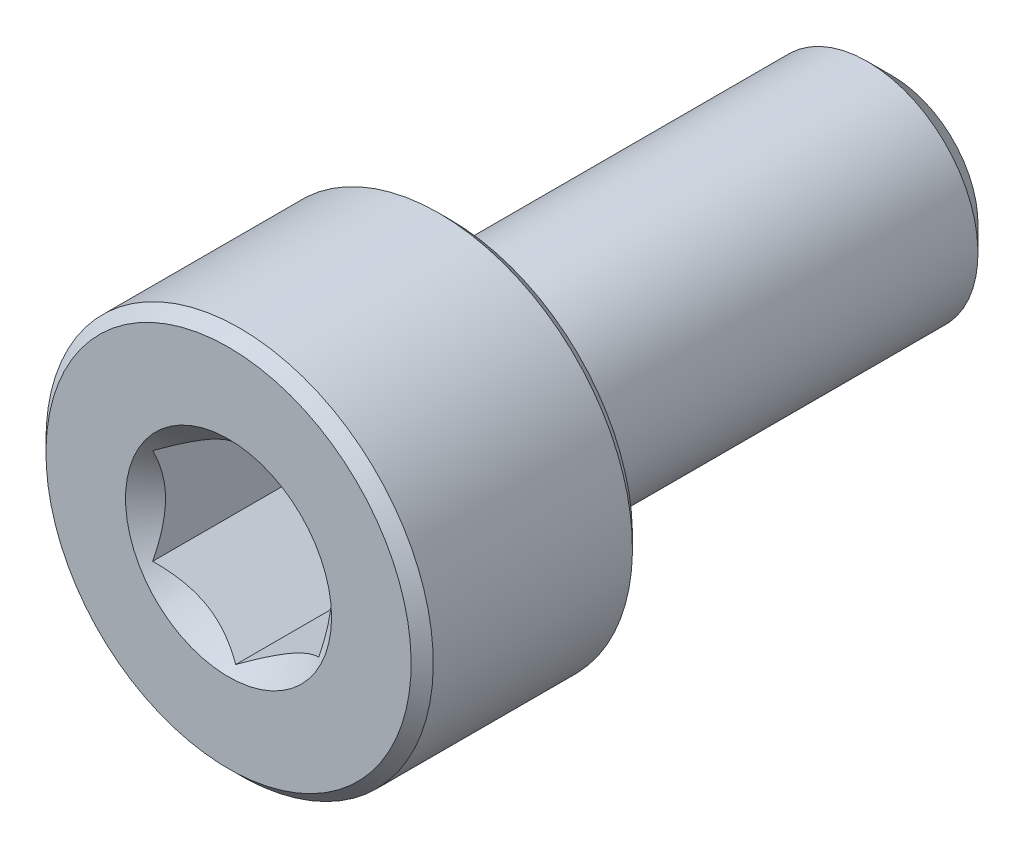
SolidWorks part; units mm, degrees
ref_plane "Front Plane" through (0, 0, 0) normal (0, 0, 1) x (1, 0, 0)
ref_plane "Top Plane" through (0, 0, 0) normal (0, 1, 0) x (1, 0, 0)
ref_plane "Right Plane" through (0, 0, 0) normal (1, 0, 0) x (0, 0, -1)
sketch "Sketch1" plane through (0, 0, 0) normal (1, 0, 0) x (0, 0, -1)
  line L0 (-6, 0) -> (6, 0) construction
  line L1 (6, 0) -> (6, 1.5453) construction
  line L2 (6, 1.5453) -> (5.5453, 2) construction
  line L3 (5.5453, 2) -> (5.475, 2) construction
  line L4 (5.475, 2) -> (-2, 2) construction
  line L5 (-2, 2) -> (-2, 3.5) construction
  line L6 (-2, 3.5) -> (-6, 3.5) construction
  line L7 (-6, 3.5) -> (-6, 0) construction
  line L8 (6, 1.5453) -> (6, 2) construction
  line L9 (5.9562, 2.0758) -> (6.3062, 1.4696) construction
  line L10 (6.3062, 1.4696) -> (6.6562, 2.0758) construction
  line L11 (6.6562, 2.0758) -> (5.9562, 2.0758) construction
  line L12 (6.3062, 2.0758) -> (6.3063, 2) construction
  line L13 (6.3062, 1.4696) -> (6.3062, 1.5453) construction
  line L14 (6.2625, 1.5453) -> (6.35, 1.5453) construction
  line L15 (6, 2) -> (6.6125, 2) construction
  line L16 (5.9781, 2.0379) -> (6.6344, 2.0379) construction
  line L17 (6, 0) -> (6, -2) construction
  line L18 (-2.2, 3.5) -> (-2, 3.3) construction
  line L19 (-5.8, 3.5) -> (-6, 3.3) construction
  line L20 (-2, 2) -> (-2, 0) construction
  line L21 (-2, 1) -> (0.6667, 1) construction
  line L22 (0.6667, 1) -> (3.3333, 1) construction
  line L23 (3.3333, 1) -> (6, 1) construction
  line L24 (0.6667, 1) -> (0.6667, 2) construction
  line L25 (0.6667, 2) -> (0.6667, 3.5) construction
  line L26 (3.3333, 1) -> (3.3333, 3.5) construction
  point P0 (-6, 1.5)
  point P3 (4.25, 2)
  point P4 (0, 0)
  point P18 (3.3333, 2)
  point P22 (6.3062, 1.5453)
  point P24 (5.475, 2)
  point P25 (6.3063, 2)
  point P28 (6.3063, 2.0379)
  point P29 (4.25, -2)
  point P30 (0.6667, 2)
  point P31 (-4, 3.5)
  point P37 (-2.7, 3.5)
  point P38 (-5.7, 3.5)
  point P45 (0.6667, 1)
  point P46 (3.3333, 1)
  dimension "D2" = 0.0875
  dimension "D7" = 0.2
  dimension "D8" = 0.2
  dimension "D9" = 0.2
  dimension "D10" = 0.1
  dimension "D11" = 0.5
  dimension "Drive Size" = 3
  dimension "Head Diameter" = 7
  dimension "Head Height" = 4
  dimension "Thread Pitch" = 0.7
  dimension "Thread Size" = 4
  dimension "Length" = 8
  dimension "D12" = 0.525
  dimension "D4" = 1.75
  dimension "D3" = 45
sketch "Sketch2" plane through (0, 0, 0) normal (1, 0, 0) x (0, 0, -1)
  line L0 (-6, 0) -> (-6, 3.3)
  line L1 (-5.8, 3.5) -> (-2.2, 3.5)
  line L2 (-2, 3.3) -> (-2, 2.2)
  line L4 (5.5453, 2) -> (6, 1.5453)
  line L5 (6, 1.5453) -> (6, 0)
  line L6 (-2, 3.5) -> (-6, 3.5) construction
  line L7 (6, 0) -> (-6, 0)
  line L8 (-5.8, 3.5) -> (-6, 3.3) construction
  line L10 (-5.8, 3.5) -> (-6, 3.3)
  line L14 (-2.2, 3.5) -> (-2, 3.3) construction
  line L16 (-2.2, 3.5) -> (-2, 3.3)
  line L17 (-2, 2) -> (-2, 3.5) construction
  line L19 (-1.8, 2) -> (5.5453, 2)
  line L20 (5.475, 2) -> (-2, 2) construction
  arc A1 (-2, 2.2) -> (-1.8, 2) centre (-1.8, 2.2) ccw
  dimension "D3" = 0.2
revolve "Revolve1" add sketch "Sketch2" angle 360 about L7
sketch "Sketch3" plane through (0, 0, 6) normal (0, 0, 1) x (1, 0, 0)
  line L1 (1.5, -0.866) -> (1.5, 0.866)
  line L2 (1.5, 0.866) -> (0, 1.7321)
  line L3 (0, 1.7321) -> (-1.5, 0.866)
  line L4 (-1.5, 0.866) -> (-1.5, -0.866)
  line L5 (-1.5, -0.866) -> (0, -1.7321)
  line L6 (0, -1.7321) -> (1.5, -0.866)
  circle A0 centre (0, 0) radius 1.5 construction
  circle A1 centre (0, 0) radius 3.5 construction
  circle A2 centre (0, 0) radius 3.5 construction
  circle A3 centre (0, 0) radius 1.7321 construction
  point P13 (0, 0)
  dimension "D1" = 3.4641
extrude "Cut-Extrude1" cut sketch "Sketch3" against normal offset from surface (3 mm away) 1 up to face at (0, 3.3, 2)
sketch "Sketch4" plane through (0, 0, 6) normal (0, 0, 1) x (1, 0, 0)
  circle A0 centre (0, 0) radius 1.862
  dimension "D1" = 3.7239
extrude "Cut-Extrude2" cut sketch "Sketch4" against normal up to vertex (2 mm away) draft 45 up to point (0, 3.5, 4)
sketch "Sketch11" plane through (0, 0, 0) normal (1, 0, 0) x (0, 0, -1)
  line L0 (-6, 0) -> (6, 0) construction
  line L1 (-6, 0) -> (6, 0) construction
  line L2 (-0.5, 0) -> (-0.5, 2) construction
  line L3 (5.475, 2) -> (-2, 2) construction
  line L4 (4.5, 0) -> (4.5, 2) construction
  line L6 (6, 1.5453) -> (6, 2) construction
  point P2 (-0.5, 0)
  point P3 (4.5, 0)
  dimension "D1" = 1.5
  dimension "D2" = 1.5
sketch "Sketch6" [suppressed] plane through (0, 0, -6) normal (0, 0, -1) x (-1, 0, 0)
  circle A0 centre (0, 0) radius 2
curve "Helix/Spiral1" [suppressed] pitch 0.7 height 8.7 turns 12.4286
sketch "Sketch10" [suppressed] plane through (0, 0, 0) normal (1, 0, 0) x (0, 0, -1)
  line L0 (-1.8, -3.5) -> (-1.8, 3.5)
  line L5 (-6, 0) -> (6, 0) construction
  line L6 (-1.8, 2) -> (-1.8, -2) construction
  point P3 (-1.8, 0)
split "Split1" [suppressed] bodies to split 106
sketch "Sketch7" [suppressed] plane through (0, 0, 0) normal (1, 0, 0) x (0, 0, -1)
  line L0 (5.9781, 2.0379) -> (6.6344, 2.0379)
  line L1 (6.6344, 2.0379) -> (6.35, 1.5453)
  line L2 (6.35, 1.5453) -> (6.2625, 1.5453)
  line L3 (6.2625, 1.5453) -> (5.9781, 2.0379)
sweep "Cut-Sweep1" [suppressed] cut profiles "Sketch7" path "Helix/Spiral1"
sketch "Sketch8" [suppressed] plane through (0, 0, 0) normal (1, 0, 0) x (0, 0, -1)
  line L0 (-2, 0) -> (-2, 2)
  line L1 (-1.8, -2) -> (-1.8, 2) construction
  line L2 (-2, 2) -> (-1.8, 2)
  line L4 (-1.8, 2) -> (-0.6453, 0)
  line L5 (-0.6453, 0) -> (-2, 0)
  line L6 (5.475, 2) -> (-2, 2) construction
  line L7 (-6, 0) -> (6, 0) construction
  dimension "D1" = 60
revolve "Revolve2" [suppressed] add sketch "Sketch8" angle 360 about L5
equation "\"D2@Sketch1\" = \"Thread Pitch@Sketch1\" / 8"
equation "\"D4@Helix/Spiral1\" = \"Thread Pitch@Sketch1\""
equation "\"D7@Sketch1\" = \"Head Height@Sketch1\" * .05"
equation "\"D8@Sketch1\"=\"D7@Sketch1\""
equation "\"D9@Sketch1\"=\"D7@Sketch1\""
equation "\"D10@Sketch1\"=\"D7@Sketch1\"/2"
equation "\"D11@Sketch1\"=\"D10@Sketch1\"*5"
equation "\"D4@Sketch1\"=\"Thread Pitch@Sketch1\"*2.5"
equation "\"D12@Sketch1\"=\"Thread Pitch@Sketch1\"*.75"
equation "\"D3@Helix/Spiral1\"=\"Length@Sketch1\"+\"Thread Pitch@Sketch1\""
equation "\"D3@Sketch2\"=\"Thread Size@Sketch1\"*0.05"
equation "\"D1@Sketch11\"=\"Length@Sketch1\"*0.1875"
equation "\"D2@Sketch11\"=\"D1@Sketch11\""
equation "\"D1@Sketch4\"=\"D1@Sketch3\"*1.075"
